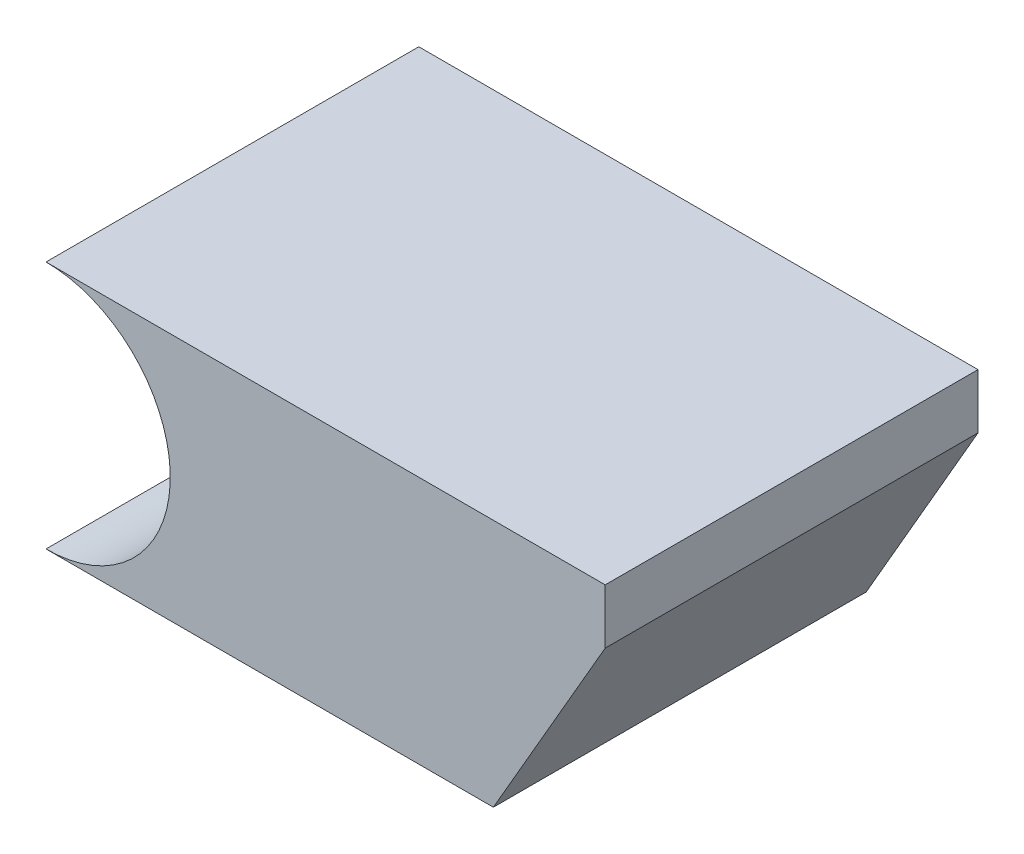
SolidWorks part; units mm, degrees
ref_plane "Front Plane" through (0, 0, 0) normal (0, 0, 1) x (1, 0, 0)
ref_plane "Top Plane" through (0, 0, 0) normal (0, 1, 0) x (1, 0, 0)
ref_plane "Right Plane" through (0, 0, 0) normal (1, 0, 0) x (0, 0, -1)
sketch "Sketch1" plane through (0, 0, 0) normal (0, 0, 1) x (1, 0, 0)
  line L1 (0, 0) -> (57.15, 0)
  line L3 (0, 25.4) -> (57.15, 25.4)
  line L4 (57.15, 0) -> (57.15, 25.4)
  arc A1 (0, 0) -> (0, 25.4) centre (0, 12.7) ccw
  dimension "D2" = 25.4
  dimension "D1" = 57.15
extrude "Boss-Extrude1" add sketch "Sketch1" along normal blind 38.1
chamfer "Chamfer1" distance 11.43 angle 60 1 edges at (57.15, 0, 19.05) first distance on face at (28.575, 0, 19.05)
